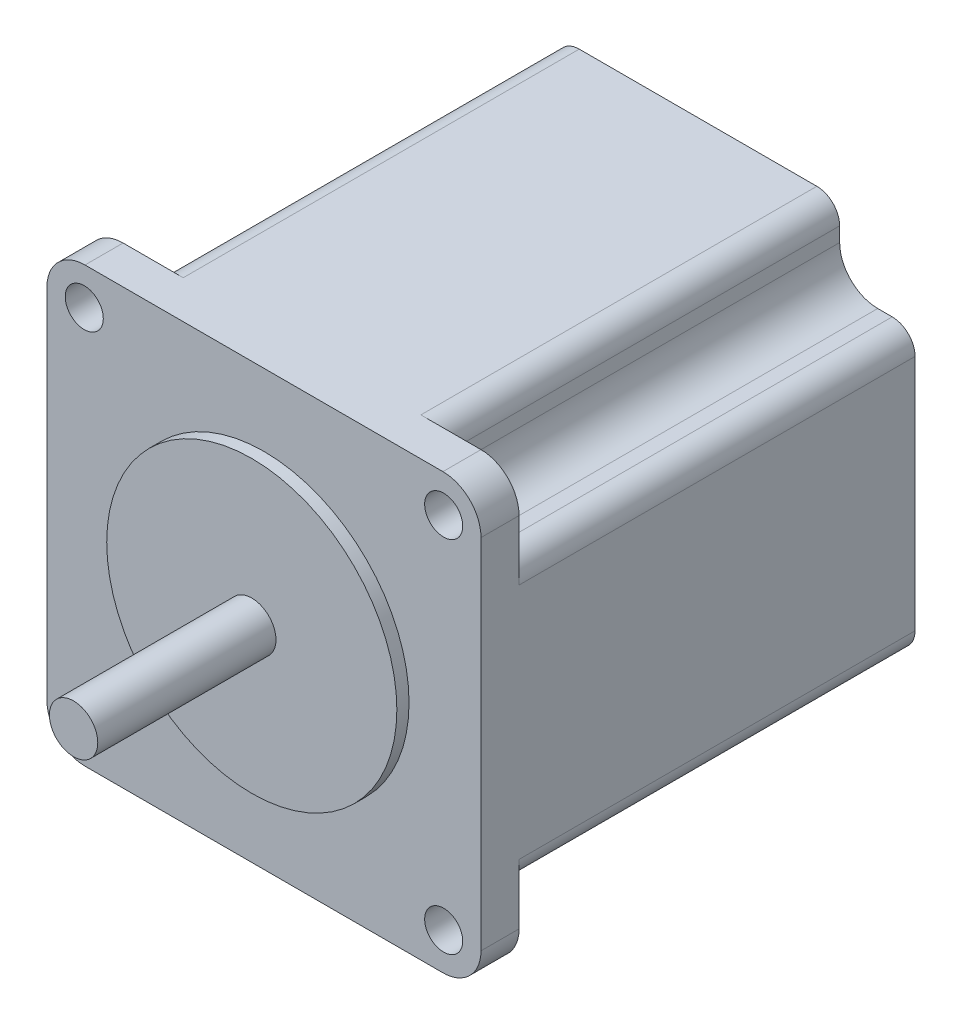
SolidWorks part; units mm, degrees
ref_plane "Front Plane" through (0, 0, 0) normal (0, 0, 1) x (1, 0, 0)
ref_plane "Top Plane" through (0, 0, 0) normal (0, 1, 0) x (1, 0, 0)
ref_plane "Right Plane" through (0, 0, 0) normal (1, 0, 0) x (0, 0, -1)
sketch "Sketch1" plane through (0, 0, 0) normal (0, 0, 1) x (1, 0, 0)
  line L1 (-23.5, -28.5) -> (23.5, -28.5)
  line L2 (-28.5, -23.5) -> (-28.5, 23.5)
  line L3 (-23.5, 28.5) -> (23.5, 28.5)
  line L4 (28.5, -23.5) -> (28.5, 23.5)
  line L5 (-28.5, -28.5) -> (28.5, 28.5) construction
  line L6 (-28.5, 28.5) -> (28.5, -28.5) construction
  line L11 (-23.57, -23.57) -> (23.57, 23.57) construction
  line L12 (-23.57, 23.57) -> (23.57, -23.57) construction
  arc A0 (-23.5, -28.5) -> (-28.5, -23.5) centre (-23.5, -23.5) cw
  arc A1 (23.5, -28.5) -> (28.5, -23.5) centre (23.5, -23.5) ccw
  arc A2 (23.5, 28.5) -> (28.5, 23.5) centre (23.5, 23.5) cw
  arc A3 (-23.5, 28.5) -> (-28.5, 23.5) centre (-23.5, 23.5) ccw
  point P0 (0, 0)
  point P18 (0, 0)
  dimension "D3" = 5
  dimension "D1" = 57
  dimension "D2" = 57
extrude "Boss-Extrude1" add sketch "Sketch1" along normal mid plane 5
sketch "Sketch5" plane through (0, 0, 2.5) normal (0, 0, 1) x (1, 0, 0)
  line L1 (-23.6, -23.6) -> (23.6, -23.6) construction
  line L2 (-23.6, -23.6) -> (-23.6, 23.6) construction
  line L3 (-23.6, 23.6) -> (23.6, 23.6) construction
  line L4 (23.6, -23.6) -> (23.6, 23.6) construction
  line L5 (-23.6, -23.6) -> (23.6, 23.6) construction
  line L6 (-23.6, 23.6) -> (23.6, -23.6) construction
  circle A0 centre (-23.6, 23.6) radius 2.5
  circle A1 centre (23.6, 23.6) radius 2.5
  circle A2 centre (23.6, -23.6) radius 2.5
  circle A3 centre (-23.6, -23.6) radius 2.5
  point P0 (0, 0)
  dimension "D3" = 5
  dimension "D4" = 5
  dimension "D5" = 5
  dimension "D6" = 5
  dimension "D1" = 47.2
  dimension "D2" = 47.2
extrude "Cut-Extrude1" cut sketch "Sketch5" against normal through all
sketch "Sketch2" plane through (0, 0, 2.5) normal (0, 0, 1) x (1, 0, 0)
  circle A0 centre (0, 0) radius 3.175
  dimension "D1" = 6.35
extrude "Boss-Extrude2" add sketch "Sketch2" along normal blind 25
sketch "Sketch3" plane through (0, 0, 2.5) normal (0, 0, 1) x (1, 0, 0)
  circle A0 centre (0, 0) radius 19.05
  dimension "D1" = 38.1
extrude "Boss-Extrude3" add sketch "Sketch3" along normal blind 1.6
sketch "Sketch4" plane through (0, 0, -2.5) normal (0, 0, -1) x (-1, 0, 0)
  line L0 (-18.6, 23.6) -> (-18.6, 25.5)
  line L1 (-23.5, 28.5) -> (23.5, 28.5) construction
  line L2 (-15.6, 28.5) -> (15.6, 28.5)
  line L3 (18.6, 25.5) -> (18.6, 23.6)
  line L4 (23.6, 18.6) -> (25.5, 18.6)
  line L5 (28.5, 23.5) -> (28.5, -23.5) construction
  line L6 (28.5, 15.6) -> (28.5, -15.6)
  line L7 (25.5, -18.6) -> (23.6, -18.6)
  line L8 (18.6, -23.6) -> (18.6, -25.5)
  line L9 (23.5, -28.5) -> (-23.5, -28.5) construction
  line L10 (15.6, -28.5) -> (-15.6, -28.5)
  line L11 (-18.6, -25.5) -> (-18.6, -23.6)
  line L12 (-23.6, -18.6) -> (-25.5, -18.6)
  line L13 (-28.5, -23.5) -> (-28.5, 23.5) construction
  line L14 (-28.5, -15.6) -> (-28.5, 15.6)
  line L15 (-25.5, 18.6) -> (-23.6, 18.6)
  arc A0 (-23.6, 18.6) -> (-18.6, 23.6) centre (-23.6, 23.6) ccw
  arc A1 (18.6, 23.6) -> (23.6, 18.6) centre (23.6, 23.6) ccw
  arc A2 (23.6, -18.6) -> (18.6, -23.6) centre (23.6, -23.6) ccw
  arc A3 (-18.6, -23.6) -> (-23.6, -18.6) centre (-23.6, -23.6) ccw
  arc A4 (-28.5, 15.6) -> (-25.5, 18.6) centre (-25.5, 15.6) cw
  arc A5 (-18.6, 25.5) -> (-15.6, 28.5) centre (-15.6, 25.5) cw
  arc A6 (15.6, 28.5) -> (18.6, 25.5) centre (15.6, 25.5) cw
  arc A7 (28.5, 15.6) -> (25.5, 18.6) centre (25.5, 15.6) ccw
  arc A8 (28.5, -15.6) -> (25.5, -18.6) centre (25.5, -15.6) cw
  arc A9 (15.6, -28.5) -> (18.6, -25.5) centre (15.6, -25.5) ccw
  arc A10 (-15.6, -28.5) -> (-18.6, -25.5) centre (-15.6, -25.5) cw
  arc A11 (-25.5, -18.6) -> (-28.5, -15.6) centre (-25.5, -15.6) cw
  circle A12 centre (23.6, 23.6) radius 2.5 construction
  circle A13 centre (-23.6, 23.6) radius 2.5 construction
  circle A14 centre (23.6, -23.6) radius 2.5 construction
  circle A15 centre (-23.6, -23.6) radius 2.5 construction
  point P7 (-28.5, 18.6)
  point P37 (-18.6, 28.5)
  point P40 (18.6, 28.5)
  point P43 (28.5, 18.6)
  point P46 (28.5, -18.6)
  point P49 (18.6, -28.5)
  point P52 (-18.6, -28.5)
  point P55 (-28.5, -18.6)
  dimension "D1" = 10
  dimension "D2" = 10
  dimension "D3" = 10
  dimension "D4" = 10
  dimension "D5" = 3
extrude "Boss-Extrude4" add sketch "Sketch4" along normal blind 52
